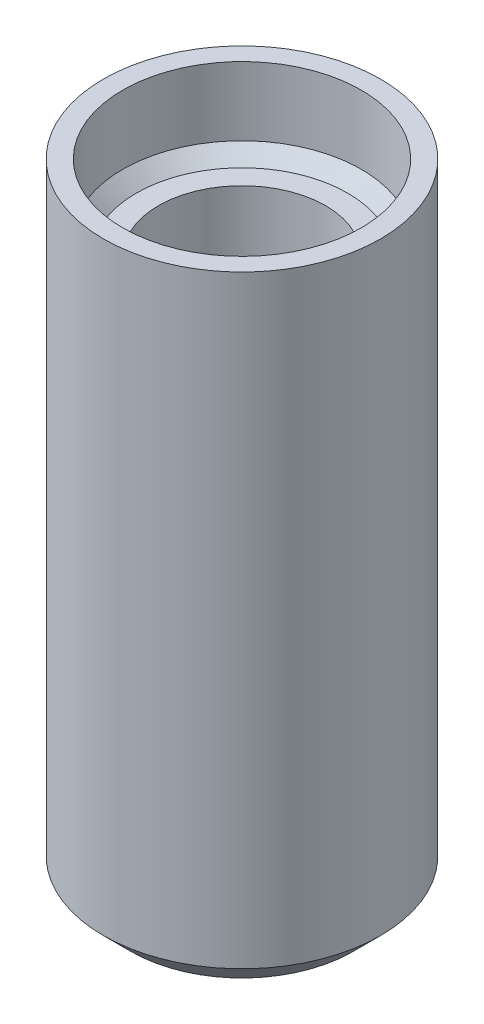
SolidWorks part; units mm, degrees
ref_plane "Front Plane" through (0, 0, 0) normal (0, 0, 1) x (1, 0, 0)
ref_plane "Top Plane" through (0, 0, 0) normal (0, 1, 0) x (1, 0, 0)
ref_plane "Right Plane" through (0, 0, 0) normal (1, 0, 0) x (0, 0, -1)
sketch "Sketch1" plane through (0, 0, 0) normal (0, 1, 0) x (1, 0, 0)
  line L0 (-2.5652, -1.65) -> (2.5652, -1.65)
  circle A0 centre (0, 0) radius 3.05
  circle A1 centre (0, 0) radius 5.05
  dimension "D1" = 6.1
  dimension "D3" = 1.65
  dimension "D2" = 2
extrude "Boss-Extrude1" add sketch "Sketch1" along normal blind 20 contours A1 A0 | L0 A0 region at (0, 0, 2.2227) region at (-4.9072, 0, 0)
sketch "Sketch2" plane through (0, 0, 0) normal (0, -1, 0) x (1, 0, 0)
  circle A1 centre (0, 0) radius 5.05
  circle A2 centre (0, 0) radius 5.05
  dimension "D1" = 0
extrude "Boss-Extrude2" add sketch "Sketch2" against normal blind 2
sketch "Sketch4" plane through (0, 20, 0) normal (0, 1, 0) x (1, 0, 0)
  circle A0 centre (0, 0) radius 4.35
  circle A1 centre (0, 0) radius 5.05
  circle A2 centre (0, 0) radius 5.05
  dimension "D1" = 0
  dimension "D2" = 0.7
extrude "Boss-Extrude3" add sketch "Sketch4" along normal blind 3
chamfer "Chamfer1" distance 1 angle 45 1 edges at (0, 0, 5.05)
chamfer "Chamfer2" distance 0.5 angle 45 1 edges at (0, 20, 4.35)
sketch "Sketch5" plane through (0, 0, 0) normal (0, -1, 0) x (1, 0, 0)
  line L0 (-1.326, 0) -> (1.326, 0) construction
  line L1 (-3.5217, -2) -> (3.5217, -2) construction
  circle A0 centre (0, 0) radius 4.05 construction
  text T0 "<b>8</b>" font "Calibri" height in points 16
  dimension "D1" = 2
extrude "Cut-Extrude1" cut sketch "Sketch5" against normal blind 0.4
extrude "Boss-Extrude4" add sketch "Sketch5<2>" against normal blind 0.4 separate body
sketch "Sketch5<2>" plane through (0, 0, 0) normal (0, -1, 0) x (1, 0, 0) same geometry as "Sketch5"
equation "\"ID\"= 6.3"
equation "\"notch\"= 6.3 / 2 - 1.5"
equation "\"D3@Sketch1\"=\"notch\""
